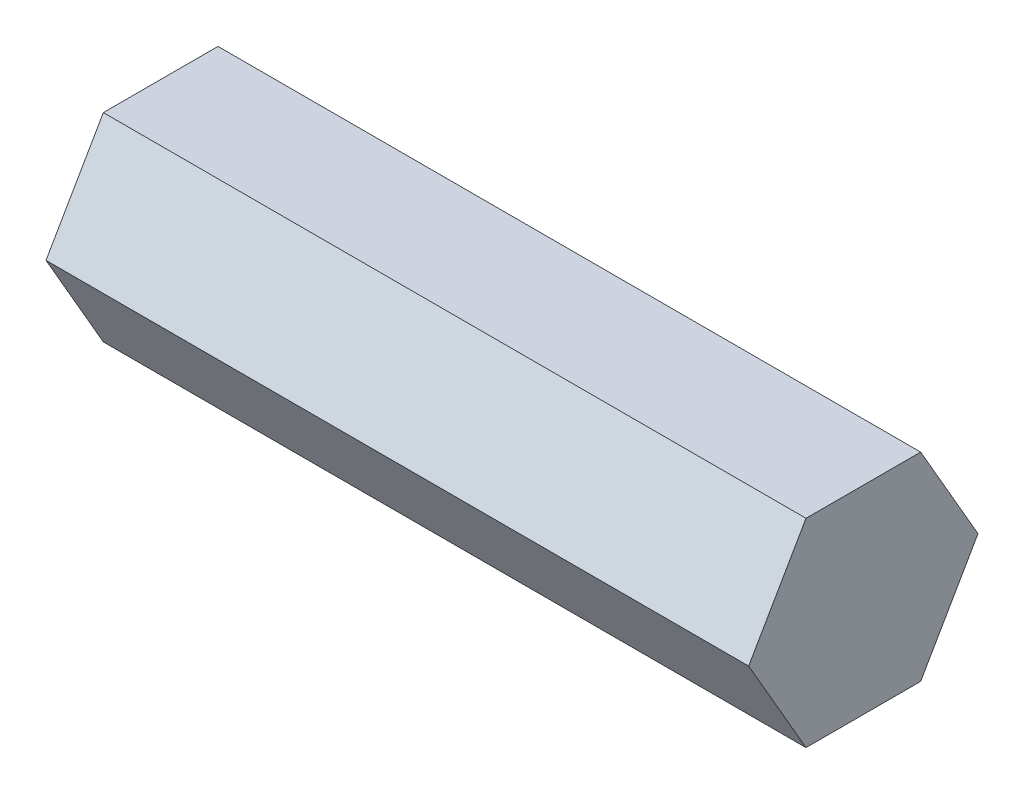
SolidWorks part; units mm, degrees
ref_plane "Alzado" through (0, 0, 0) normal (0, 0, 1) x (1, 0, 0)
ref_plane "Planta" through (0, 0, 0) normal (0, 1, 0) x (1, 0, 0)
ref_plane "Vista lateral" through (0, 0, 0) normal (1, 0, 0) x (0, 0, -1)
sketch "Croquis2" plane through (0, 0, 0) normal (1, 0, 0) x (0, 0, -1)
  line L1 (7.3323, 0) -> (3.6662, 6.35)
  line L2 (3.6662, 6.35) -> (-3.6662, 6.35)
  line L3 (-3.6662, 6.35) -> (-7.3323, 0)
  line L4 (-7.3323, 0) -> (-3.6662, -6.35)
  line L5 (-3.6662, -6.35) -> (3.6662, -6.35)
  line L6 (3.6662, -6.35) -> (7.3323, 0)
  circle A0 centre (0, 0) radius 6.35 construction
  dimension "D1" = 12.7
extrude "Saliente-Extruir1" add sketch "Croquis2" along normal blind 44.935
sketch "Croquis3" plane through (0, 0, 0) normal (-1, 0, 0) x (0, 0, 1)
  circle A0 centre (0, 0) radius 2.5
  dimension "D1" = 5
sketch "Croquis4" plane through (44.935, 0, 0) normal (1, 0, 0) x (0, 0, -1)
  circle A0 centre (0, 0) radius 2.5
  dimension "D1" = 5
